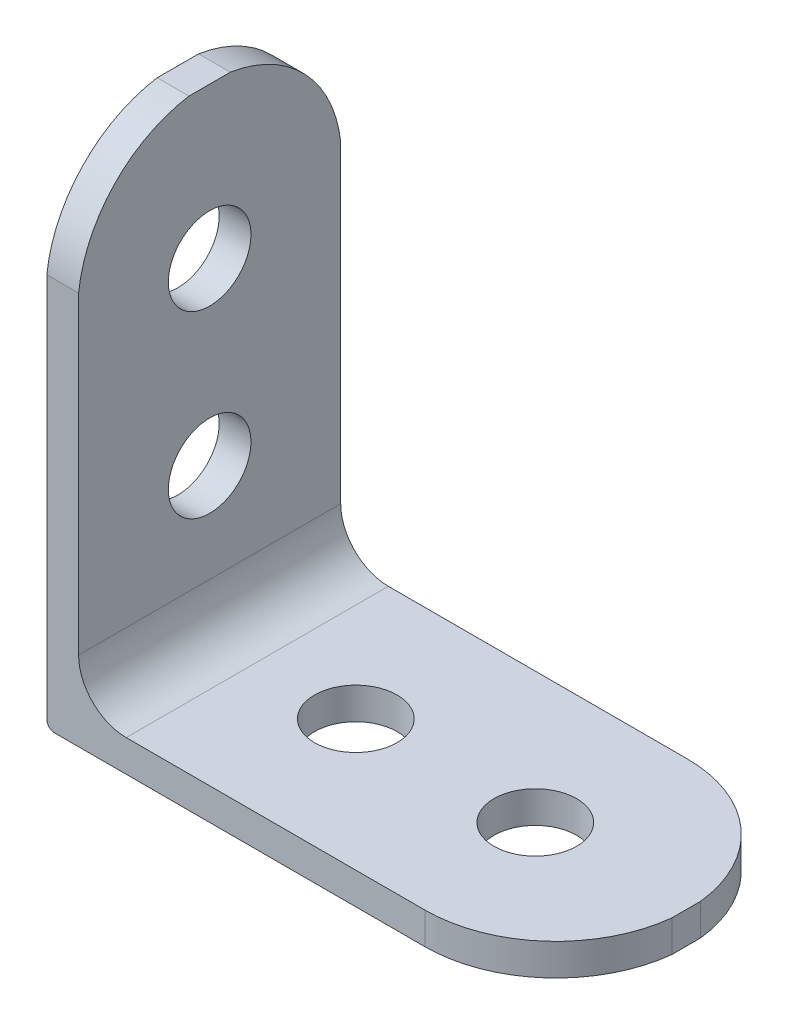
SolidWorks part; units mm, degrees
ref_plane "Plan de face" through (0, 0, 0) normal (0, 0, 1) x (1, 0, 0)
ref_plane "Plan de dessus" through (0, 0, 0) normal (0, 1, 0) x (1, 0, 0)
ref_plane "Plan de droite" through (0, 0, 0) normal (1, 0, 0) x (0, 0, -1)
sketch "Esquisse1" plane through (0, 0, 0) normal (0, 0, 1) x (1, 0, 0)
  line L0 (-3.7516, 1.453) -> (23.2484, 1.453)
  line L1 (-8.2516, -0.547) -> (23.2484, -0.547)
  line L2 (-8.7516, -0.047) -> (-8.7516, 0.2059)
  line L4 (23.2484, -0.547) -> (23.2484, 1.453)
  line L5 (-8.7516, -0.547) -> (23.2484, 1.453) construction
  line L6 (-8.7516, 0.2059) -> (23.2484, -0.547) construction
  line L8 (-8.7516, 0.2059) -> (-8.7516, 31.453)
  line L9 (-8.7516, 31.453) -> (-6.7516, 31.453)
  line L10 (-6.7516, 4.453) -> (-6.7516, 31.453)
  arc A0 (-3.7516, 1.453) -> (-6.7516, 4.453) centre (-3.7516, 4.453) cw
  arc A1 (-8.2516, -0.547) -> (-8.7516, -0.047) centre (-8.2516, -0.047) cw
  point P0 (0, 0)
  dimension "D3" = 3
  dimension "D6" = 0.5
  dimension "D1" = 2
  dimension "D2" = 32
  dimension "D4" = 2
  dimension "D5" = 32
extrude "Boss.-Extru.3" add sketch "Esquisse1" along normal blind 16.5 contours L10 L9 L8 L2 A1 L1 L4 L0 A0
sketch "Esquisse2" plane through (-8.7516, 0, 0) normal (-1, 0, 0) x (0, 0, 1)
  line L0 (8.25, 31.453) -> (8.25, -2.8737) construction
  line L1 (16.5, 31.453) -> (0, 31.453) construction
  line L2 (0, 23.253) -> (22.6954, 23.253) construction
  line L3 (0, -0.047) -> (0, 31.453) construction
  arc A0 (16.5527, 23.253) -> (-0.0527, 23.253) centre (8.25, 23.253) ccw
  dimension "D1" = 8.2
extrude "Enlèv. mat.-Extru.1" cut sketch "Esquisse2" against normal blind 10 and the other way through all flip side to cut
sketch "Esquisse3" plane through (0, -0.547, 0) normal (0, -1, 0) x (1, 0, 0)
  line L0 (-8.2516, 8.25) -> (28.5821, 8.25) construction
  line L1 (-8.2516, 16.5) -> (-8.2516, 0) construction
  line L2 (15.0484, 16.5) -> (15.0484, -3.0428) construction
  line L3 (-8.2516, 16.5) -> (23.2484, 16.5) construction
  line L4 (-8.2516, 0) -> (23.2484, 0) construction
  arc A0 (15.0484, 0) -> (15.0484, 16.5) centre (15.0484, 8.25) ccw
  dimension "D1" = 8.2
extrude "Enlèv. mat.-Extru.2" cut sketch "Esquisse3" against normal blind 10 and the other way through all flip side to cut
sketch "Esquisse4" plane through (0, -0.547, 0) normal (0, -1, 0) x (1, 0, 0)
  line L0 (-8.2516, 8.25) -> (28.3348, 8.25) construction
  line L1 (-8.2516, 16.5) -> (-8.2516, 0) construction
  line L2 (23.2484, 9.1569) -> (23.2484, 7.3431) construction
  circle A0 centre (13.7484, 8.25) radius 2.6
  circle A1 centre (2.4484, 8.25) radius 2.6
  dimension "D1" = 5.2
  dimension "D2" = 5.2
  dimension "D3" = 9.5
  dimension "D4" = 11.3
extrude "Enlèv. mat.-Extru.3" cut sketch "Esquisse4" against normal blind 10
sketch "Esquisse5" plane through (-8.7516, 0, 0) normal (-1, 0, 0) x (0, 0, 1)
  line L0 (8.25, 31.453) -> (8.25, -2.2662) construction
  line L1 (9.5521, 31.453) -> (6.9479, 31.453) construction
  circle A0 centre (8.25, 21.953) radius 2.6
  circle A1 centre (8.25, 10.653) radius 2.6
  dimension "D1" = 5.2
  dimension "D2" = 5.2
  dimension "D3" = 9.5
  dimension "D4" = 11.3
extrude "Enlèv. mat.-Extru.4" cut sketch "Esquisse5" against normal blind 10
